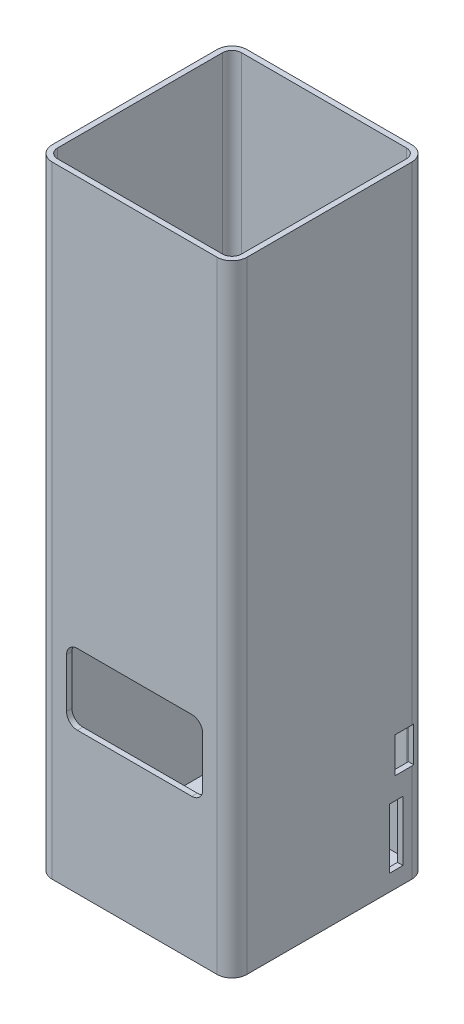
SolidWorks part; units mm, degrees
ref_plane "Ebene vorne" through (0, 0, 0) normal (0, 0, 1) x (1, 0, 0)
ref_plane "Ebene oben" through (0, 0, 0) normal (0, 1, 0) x (1, 0, 0)
ref_plane "Ebene rechts" through (0, 0, 0) normal (1, 0, 0) x (0, 0, -1)
sketch "Skizze1" plane through (0, 0, 0) normal (0, 1, 0) x (1, 0, 0)
  line L0 (-15.125, 17.875) -> (15.125, 17.875)
  line L1 (-15.125, 16.875) -> (15.125, 16.875)
  line L2 (-16.875, 15.125) -> (-16.875, -15.125)
  line L3 (-15.125, -16.875) -> (15.125, -16.875)
  line L4 (16.875, 15.125) -> (16.875, -15.125)
  line L5 (-16.875, 16.875) -> (16.875, -16.875) construction
  line L6 (-16.875, -16.875) -> (16.875, 16.875) construction
  line L7 (17.875, 15.125) -> (17.875, -15.125)
  line L8 (-15.125, -17.875) -> (15.125, -17.875)
  line L9 (-17.875, 15.125) -> (-17.875, -15.125)
  line L10 (0, 8) -> (0, -2) construction
  line L11 (-16.875, 10) -> (16.875, 10)
  line L12 (-16.875, 10) -> (-16.875, -4)
  line L13 (-16.875, -4) -> (16.875, -4)
  line L14 (16.875, 10) -> (16.875, -4)
  line L15 (-10, 8) -> (10, 8)
  line L16 (-12, 6) -> (-12, 0)
  line L17 (-10, -2) -> (10, -2)
  line L18 (12, 6) -> (12, 0)
  line L19 (0, -2) -> (0, -16.875) construction
  arc A0 (-16.875, -15.125) -> (-15.125, -16.875) centre (-15.125, -15.125) ccw
  arc A1 (15.125, -16.875) -> (16.875, -15.125) centre (15.125, -15.125) ccw
  arc A2 (15.125, 16.875) -> (16.875, 15.125) centre (15.125, 15.125) cw
  arc A3 (-15.125, 16.875) -> (-16.875, 15.125) centre (-15.125, 15.125) ccw
  arc A4 (15.125, 17.875) -> (17.875, 15.125) centre (15.125, 15.125) cw
  arc A5 (15.125, -17.875) -> (17.875, -15.125) centre (15.125, -15.125) ccw
  arc A6 (-17.875, -15.125) -> (-15.125, -17.875) centre (-15.125, -15.125) ccw
  arc A7 (-15.125, 17.875) -> (-17.875, 15.125) centre (-15.125, 15.125) ccw
  arc A8 (-12, 0) -> (-10, -2) centre (-10, 0) ccw
  arc A9 (10, -2) -> (12, 0) centre (10, 0) ccw
  arc A10 (10, 8) -> (12, 6) centre (10, 6) cw
  arc A11 (-10, 8) -> (-12, 6) centre (-10, 6) ccw
  circle A12 centre (0, -9.5) radius 3
  point P0 (0, 0)
  point P44 (12, -2)
  point P47 (12, 8)
  point P50 (-12, 8)
  dimension "D3" = 1.75
  dimension "D10" = 2
  dimension "D11" = 6
  dimension "D12" = 7.5
  dimension "D1" = 33.75
  dimension "D2" = 33.75
  dimension "D5" = 6.875
  dimension "D6" = 14
  dimension "D7" = 10
  dimension "D8" = 24
  dimension "D9" = 2
  dimension "D4" = 1
extrude "Aufsatz-Linear austragen1" add sketch "Skizze1" along normal blind 113 contours L0 A7 L9 A6 L8 A5 L7 A4 A3 L1 A2 L4 A1 L3 A0 L2 region at (0, 0, -17.3694)
extrude "Aufsatz-Linear austragen2" add sketch "Skizze1<4>" against normal blind 1 contours L0 A7 L9 A6 L8 A5 L7 A4 A3 L1 A2 L4 A1 L3 A0 L2 | L1 A3 L2 L11 L4 A2 | L2 L13 L4 L11 A11 L15 A10 L18 A9 L17 A8 L16 | L3 A1 L4 L13 L2 A0 region at (0, 0, -17.3694) region at (0, 0, -13.4201) region at (0, 0, -9.6346) region at (0, 0, 4.3612)
sketch "Skizze1<4>" plane through (0, 0, 0) normal (0, 1, 0) x (1, 0, 0) same geometry as "Skizze1"
ref_plane "Ebene1" through (0, 0, 17.875) normal (0, 0, 1) x (1, 0, 0)
sketch "Skizze2" plane through (0, 0, 17.875) normal (0, 0, 1) x (1, 0, 0)
  line L0 (0, 0) -> (0, 109.5775) construction
  line L1 (-15.125, -1) -> (15.125, -1) construction
  line L2 (-10.5, 38) -> (10.5, 38)
  line L3 (-12.5, 36) -> (-12.5, 27)
  line L4 (-10.5, 25) -> (10.5, 25)
  line L5 (12.5, 36) -> (12.5, 27)
  line L6 (-12.5, 38) -> (12.5, 25) construction
  line L7 (-12.5, 25) -> (12.5, 38) construction
  arc A0 (-12.5, 27) -> (-10.5, 25) centre (-10.5, 27) ccw
  arc A1 (10.5, 25) -> (12.5, 27) centre (10.5, 27) ccw
  arc A2 (10.5, 38) -> (12.5, 36) centre (10.5, 36) cw
  arc A3 (-10.5, 38) -> (-12.5, 36) centre (-10.5, 36) ccw
  point P3 (0, 31.5)
  dimension "D4" = 2
  dimension "D1" = 13
  dimension "D2" = 25
  dimension "D3" = 26
extrude "Schnitt-Linear austragen1" cut sketch "Skizze2" against normal blind 1
ref_plane "Ebene3" through (17.875, 0, 0) normal (1, 0, 0) x (0, 0, -1)
sketch "Skizze3" plane through (17.875, 0, 0) normal (1, 0, 0) x (0, 0, -1)
  line L0 (15.125, -1) -> (-15.125, -1) construction
  line L1 (11, 13) -> (13.5, 13)
  line L2 (11, 13) -> (11, 2)
  line L3 (11, 2) -> (13.5, 2)
  line L4 (13.5, 13) -> (13.5, 2)
  line L6 (17.875, 113) -> (17.875, -1) construction
  line L8 (12, 23.5) -> (15.5, 23.5)
  line L9 (12, 23.5) -> (12, 17)
  line L10 (12, 17) -> (15.5, 17)
  line L11 (15.5, 23.5) -> (15.5, 17)
  dimension "D1" = 2.5
  dimension "D2" = 11
  dimension "D3" = 3
  dimension "D4" = 6.875
  dimension "D5" = 3.5
  dimension "D6" = 6.5
  dimension "D7" = 1
  dimension "D8" = 4
extrude "Schnitt-Linear austragen2" cut sketch "Skizze3" against normal blind 2
